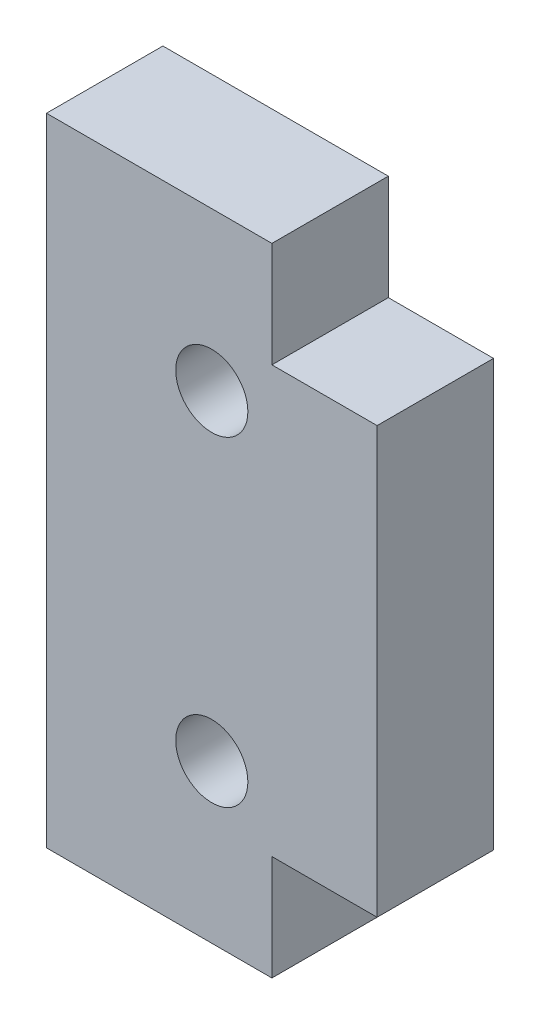
SolidWorks part; units mm, degrees
ref_plane "Front Plane" through (0, 0, 0) normal (0, 0, 1) x (1, 0, 0)
ref_plane "Top Plane" through (0, 0, 0) normal (0, 1, 0) x (1, 0, 0)
ref_plane "Right Plane" through (0, 0, 0) normal (1, 0, 0) x (0, 0, -1)
sketch "Sketch2" plane through (0, 0, 0) normal (0, 0, 1) x (1, 0, 0)
  line L0 (8.25, -152.4) -> (8.25, 152.4) construction
  line L1 (8.25, -39.1052) -> (-8.25, -39.1052)
  line L2 (8.25, -39.1052) -> (8.25, -7.3552)
  line L3 (8.25, -7.3552) -> (-8.25, -7.3552)
  line L4 (-8.25, -39.1052) -> (-8.25, -7.3552)
  line L5 (-8.25, -152.4) -> (-8.25, 152.4) construction
extrude "Boss-Extrude1" add sketch "Sketch2" along normal up to surface (5.81 mm away)
sketch "Sketch3" plane through (0, 0, 5.81) normal (0, 0, 1) x (1, 0, 0)
  line L0 (3.6, -31.2302) -> (3.6, -15.2302) construction
  line L1 (3.6, -34.8302) -> (-3.6, -34.8302)
  line L2 (3.6, -34.8302) -> (3.6, -11.6302)
  line L3 (3.6, -11.6302) -> (-3.6, -11.6302)
  line L4 (-3.6, -34.8302) -> (-3.6, -11.6302)
  line L5 (-4.4, -34.8302) -> (0, -34.8302) construction
  line L6 (0, -11.6302) -> (-4.4, -11.6302) construction
  circle A0 centre (0, -31.2302) radius 2.4 construction
  point P4 (4.1039, -35.0608)
  dimension "D1" = 3.6
extrude "Boss-Extrude2" [suppressed] add sketch "Sketch3" along normal up to surface (6 mm away)
sketch "Sketch4" [suppressed] plane through (0, 0, 11.81) normal (0, 0, 1) x (1, 0, 0)
  circle A4 centre (0, -31.2302) radius 2.8
  circle A5 centre (0, -15.2302) radius 2.8
extrude "Cut-Extrude1" [suppressed] cut sketch "Sketch4" against normal through all
sketch "Sketch5" plane through (0, 0, 5.81) normal (0, 0, 1) x (1, 0, 0)
  line L0 (3, -152.4) -> (3, 152.4) construction
  line L1 (8.25, -39.1052) -> (3, -39.1052)
  line L2 (8.25, -39.1052) -> (8.25, -33.8552)
  line L3 (8.25, -33.8552) -> (3, -33.8552)
  line L4 (3, -39.1052) -> (3, -33.8552)
  line L5 (8.25, -7.3552) -> (3, -7.3552)
  line L6 (8.25, -7.3552) -> (8.25, -12.6052)
  line L7 (8.25, -12.6052) -> (3, -12.6052)
  line L8 (3, -7.3552) -> (3, -12.6052)
extrude "Cut-Extrude2" cut sketch "Sketch5" against normal through all
sketch "Sketch6" plane through (0, 0, 5.81) normal (0, 0, 1) x (1, 0, 0)
  circle A0 centre (0, -15.2302) radius 2.4 construction
  circle A1 centre (0, -31.2302) radius 2.4 construction
  circle A2 centre (0, -15.2302) radius 2.4 construction
  circle A3 centre (0, -31.2302) radius 2.4 construction
  circle A4 centre (0, -31.2302) radius 1.8
  circle A5 centre (0, -15.2302) radius 1.8
  dimension "D1" = 0.6
extrude "Cut-Extrude3" cut sketch "Sketch6" against normal through all
